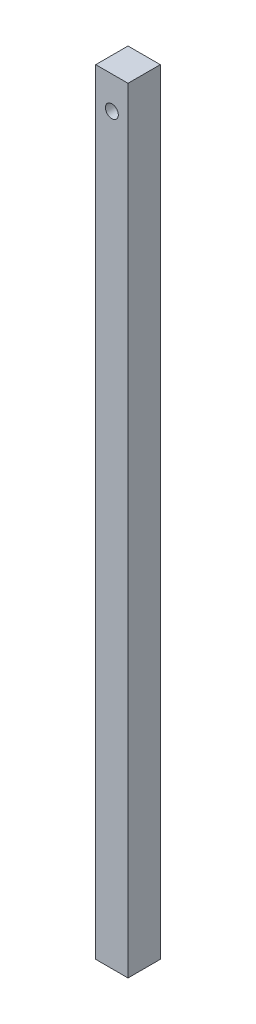
SolidWorks part; units mm, degrees
material "Brass"
ref_plane "Front Plane" through (0, 0, 0) normal (0, 0, 1) x (1, 0, 0)
ref_plane "Top Plane" through (0, 0, 0) normal (0, 1, 0) x (1, 0, 0)
ref_plane "Right Plane" through (0, 0, 0) normal (1, 0, 0) x (0, 0, -1)
sketch "Sketch1" plane through (0, 0, 0) normal (0, 0, 1) x (1, 0, 0)
  line L0 (-2.5, 0) -> (2.5, 0)
  line L1 (2.5, 0) -> (2.5, 120)
  line L2 (2.5, 120) -> (-2.5, 120)
  line L3 (-2.5, 120) -> (-2.5, 0)
  dimension "D1" = 5
  dimension "D2" = 120
  dimension "D3" = 2.5
extrude "Boss-Extrude1" add sketch "Sketch1" along normal blind 5
sketch "Sketch2" plane through (0, 0, 0) normal (0, 0, 1) x (1, 0, 0)
  circle A0 centre (0, 115) radius 1
  dimension "D2" = 2
  dimension "D1" = 115
extrude "Cut-Extrude1" cut sketch "Sketch2" against normal mid plane 20
ref_axis "Axis1" through (0, 126, 0) along (0, -1, 0)
